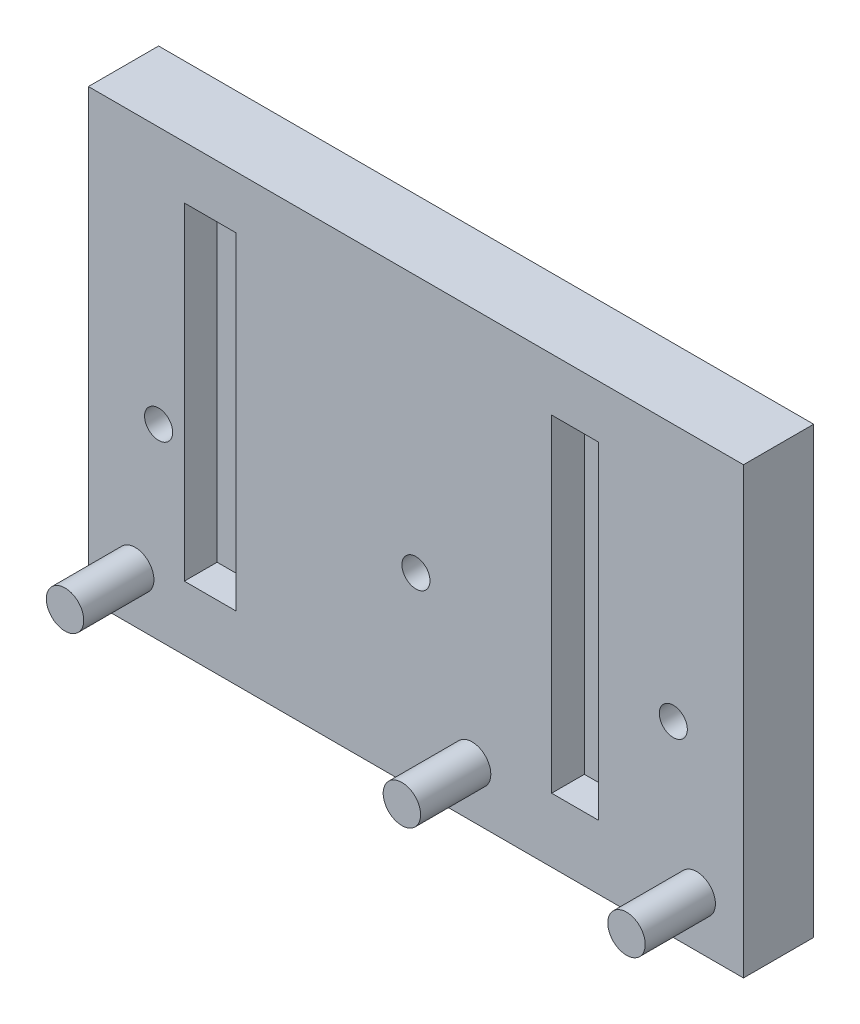
SolidWorks part; units mm, degrees
ref_plane "Front Plane" through (0, 0, 0) normal (0, 0, 1) x (1, 0, 0)
ref_plane "Top Plane" through (0, 0, 0) normal (0, 1, 0) x (1, 0, 0)
ref_plane "Right Plane" through (0, 0, 0) normal (1, 0, 0) x (0, 0, -1)
sketch "Sketch1" plane through (0, 0, 0) normal (0, 0, 1) x (1, 0, 0)
  line L0 (83.6839, -916.6433) -> (169.6839, -916.6433) construction
  line L1 (77.6839, -920.3433) -> (169.6839, -920.3433) construction
  line L2 (77.6839, -920.3433) -> (77.6839, -832.3433)
  line L3 (77.6839, -832.3433) -> (169.6839, -832.3433)
  line L4 (169.6839, -920.3433) -> (169.6839, -832.3433)
  line L5 (77.6839, -920.3433) -> (169.6839, -920.3433) construction
  line L6 (77.6839, -920.3433) -> (77.6839, -909.3433)
  line L7 (77.6839, -909.3433) -> (169.6839, -909.3433)
  line L8 (169.6839, -920.3433) -> (169.6839, -909.3433)
  line L9 (87.6839, -916.6433) -> (105.6839, -916.6433) construction
  line L10 (105.6839, -916.6433) -> (123.6839, -916.6433) construction
  line L11 (123.6839, -916.6433) -> (141.6839, -916.6433) construction
  line L12 (141.6839, -916.6433) -> (159.6839, -916.6433) construction
  line L13 (77.6839, -920.3433) -> (169.6839, -920.3433) construction
  line L14 (77.6839, -920.3433) -> (77.6839, -927.3433)
  line L15 (169.6839, -920.3433) -> (169.6839, -927.3433)
  line L16 (77.6839, -927.3433) -> (169.6839, -927.3433)
  line L17 (169.6839, -927.3433) -> (169.6839, -832.3433)
  line L18 (169.6839, -927.3433) -> (217.6839, -927.3433)
  line L19 (169.6839, -832.3433) -> (217.6839, -832.3433)
  line L20 (217.6839, -927.3433) -> (217.6839, -832.3433)
  circle A0 centre (87.6839, -916.6433) radius 4
  circle A1 centre (207.6839, -916.6433) radius 4
  circle A4 centre (159.6839, -916.6433) radius 4
  dimension "D2" = 8
  dimension "D3" = 48
  dimension "D8" = 7
  dimension "D11" = 10
  dimension "D12" = 10.7
  dimension "D9" = 10.7
  dimension "D10" = 8
  dimension "D1" = 92
  dimension "D4" = 88
  dimension "D5" = 11
  dimension "D6" = 10
  dimension "D7" = 10
extrude "Boss-Extrude1" add sketch "Sketch1" against normal blind 15 contours L2 L7 L4 L3 | L18 L20 L19 L4 L15 A1 | L14 L16 L15 L4 L7 L2 A4 A0 region at (123.6839, -918.4532, 0) region at (123.6839, -870.8433, 0) region at (193.5278, -879.4331, 0)
extrude "Boss-Extrude2" add sketch "Sketch1<3>" along normal blind 15 and the other way through all contours A0 | A4 | A1
sketch "Sketch1<3>" plane through (0, 0, 0) normal (0, 0, 1) x (1, 0, 0) same geometry as "Sketch1"
sketch "Sketch2" plane through (0, 0, 0) normal (0, 0, 1) x (1, 0, 0)
  line L0 (217.6839, -927.3433) -> (217.6839, -832.3433) construction
  line L1 (186.6839, -913.6433) -> (176.6839, -913.6433)
  line L2 (186.6839, -913.6433) -> (186.6839, -843.6433)
  line L3 (186.6839, -843.6433) -> (176.6839, -843.6433)
  line L4 (176.6839, -913.6433) -> (176.6839, -843.6433)
  line L5 (186.6839, -913.6433) -> (176.6839, -843.6433) construction
  line L6 (186.6839, -843.6433) -> (176.6839, -913.6433) construction
  line L7 (77.6839, -927.3433) -> (217.6839, -927.3433) construction
  line L8 (77.6839, -927.3433) -> (77.6839, -832.3433) construction
  line L9 (98.1839, -913.6433) -> (109.1839, -913.6433)
  line L10 (98.1839, -913.6433) -> (98.1839, -843.6433)
  line L11 (98.1839, -843.6433) -> (109.1839, -843.6433)
  line L12 (109.1839, -913.6433) -> (109.1839, -843.6433)
  line L13 (98.1839, -913.6433) -> (109.1839, -843.6433) construction
  line L14 (98.1839, -843.6433) -> (109.1839, -913.6433) construction
  line L15 (77.6839, -852.3433) -> (217.6839, -852.3433) construction
  line L16 (77.6839, -867.3433) -> (217.6839, -867.3433) construction
  line L17 (77.6839, -832.3433) -> (217.6839, -832.3433) construction
  line L18 (77.6839, -882.3433) -> (217.6839, -882.3433) construction
  line L19 (77.6839, -892.3433) -> (217.6839, -892.3433) construction
  line L20 (77.6839, -887.3433) -> (217.6839, -887.3433) construction
  circle A0 centre (92.6839, -887.3433) radius 3
  circle A1 centre (147.6839, -887.3433) radius 3
  circle A2 centre (202.6839, -887.3433) radius 3
  point P0 (181.6839, -878.6433)
  point P9 (103.6839, -878.6433)
  dimension "D14" = 6
  dimension "D15" = 6
  dimension "D16" = 6
  dimension "D17" = 15
  dimension "D18" = 15
  dimension "D1" = 31
  dimension "D2" = 70
  dimension "D3" = 10
  dimension "D4" = 13.7
  dimension "D5" = 13.7
  dimension "D6" = 20.5
  dimension "D7" = 70
  dimension "D8" = 11
  dimension "D9" = 20
  dimension "D10" = 35
  dimension "D11" = 50
  dimension "D12" = 10
  dimension "D13" = 5
extrude "Cut-Extrude1" cut sketch "Sketch2" against normal through all contours A1 | A2 | A0 region at (147.6839, -887.3433, 0) region at (202.6839, -887.3433, 0)
extrude "Cut-Extrude2" cut sketch "Sketch2<3>" against normal blind 7 contours L9 L12 L11 L10 | L4 L1 L2 L3 region at (181.6839, -878.6433, 0) region at (103.6839, -878.6433, 0)
sketch "Sketch2<3>" plane through (0, 0, 0) normal (0, 0, 1) x (1, 0, 0) same geometry as "Sketch2"
